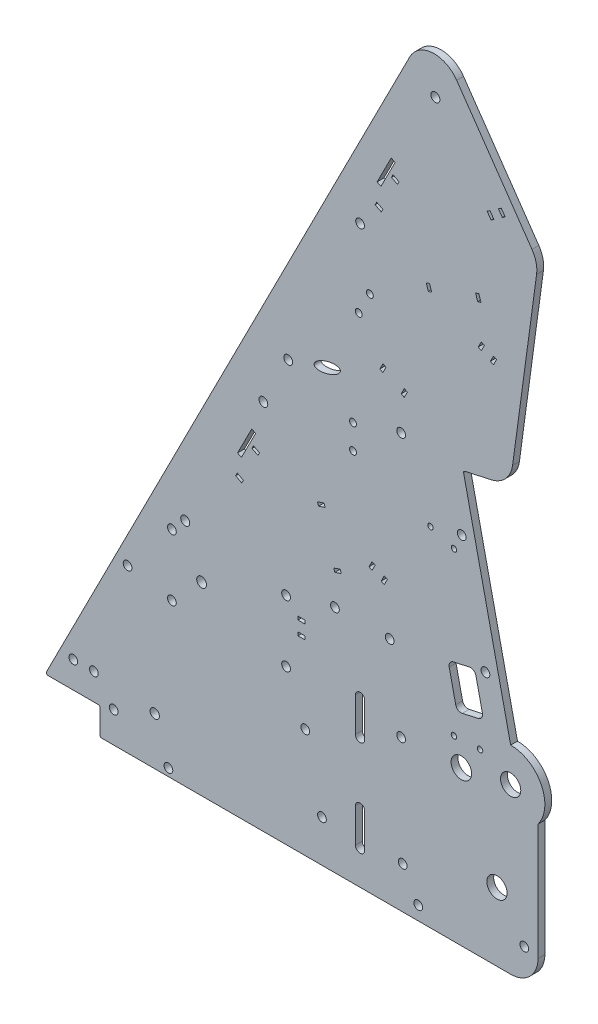
SolidWorks part; units mm, degrees
other "Markup1"
sketch "Sketch5"
ref_plane "Front Plane" through (0, 0, 0) normal (0, 0, 1) x (1, 0, 0)
ref_plane "Top Plane" through (0, 0, 0) normal (0, 1, 0) x (1, 0, 0)
ref_plane "Right Plane" through (0, 0, 0) normal (1, 0, 0) x (0, 0, -1)
sketch "Sketch1" plane through (0, 0, 0) normal (0, 0, 1) x (1, 0, 0)
  line L1 (228.6, -12.7) -> (228.6, 53.975)
  line L2 (178.7547, 351.4131) -> (0, 0)
  line L3 (228.6, 279.4) -> (178.7547, 351.4131)
  line L5 (0, 0) -> (25.4, 0)
  line L6 (25.4, 0) -> (25.4, -12.7)
  line L7 (25.4, -12.7) -> (228.6, -12.7)
  line L9 (215.9, 79.375) -> (193.9097, 178.5667)
  line L10 (193.9097, 178.5667) -> (215.6079, 183.377)
  line L11 (215.6079, 183.377) -> (228.6, 279.4)
  arc A0 (228.6, 53.975) -> (215.9, 79.375) centre (215.9, 63.5) ccw
  dimension "D7" = 12.7
  dimension "D8" = 76.2
  dimension "D10" = 31.75
  dimension "D2" = 292.1
  dimension "D3" = 25.4
  dimension "D4" = 215.9
  dimension "D5" = 394.2644
  dimension "D6" = 203.2
  dimension "D9" = 63.039
  dimension "D11" = 101.6
  dimension "D12" = 12.5
  dimension "D13" = 22.225
extrude "Boss-Extrude1" add sketch "Sketch1" along normal blind 3.175
sketch "Sketch2" plane through (0, 0, 3.175) normal (0, 0, 1) x (1, 0, 0)
  line L0 (178.7547, 351.4131) -> (0, 0) construction
  line L1 (25.4, -12.7) -> (228.6, -12.7) construction
  line L2 (215.9, 79.375) -> (193.9097, 178.5667) construction
  line L3 (193.9097, 178.5667) -> (215.6079, 183.377) construction
  line L4 (215.9, 79.375) -> (193.9097, 178.5667) construction
  line L5 (64.9432, 94.0578) -> (72.5445, 73.1732) construction
  line L6 (64.9432, 94.0578) -> (103.3734, 94.0578) construction
  line L10 (228.6, -12.7) -> (228.6, 53.975) construction
  circle A0 centre (64.9432, 94.0578) radius 2.0955
  circle A1 centre (180.975, 322.1643) radius 2.0955
  circle A2 centre (72.5445, 73.1732) radius 2.286
  circle A3 centre (193.2078, 152.3944) radius 2.032
  circle A4 centre (215.9, 63.5) radius 4.699
  circle A7 centre (173.0375, -6.35) radius 2.032
  circle A8 centre (204.203, 102.7985) radius 2.032
  circle A26 centre (209.55, 19.05) radius 4.699
  arc A30 (228.6, 53.975) -> (215.9, 79.375) centre (215.9, 63.5) ccw construction
  circle A31 centre (165.1, 179.3875) radius 2.032
  circle A35 centre (111.724, 87.4607) radius 2.032
  circle A36 centre (111.724, 58.8857) radius 2.032
  circle A37 centre (58.765, 58.8857) radius 2.032
  circle A38 centre (58.765, 87.4607) radius 2.032
  circle A39 centre (111.724, 58.8857) radius 1.905 construction
  circle A42 centre (111.724, 87.4607) radius 1.905 construction
  circle A43 centre (58.765, 58.8857) radius 1.905 construction
  circle A44 centre (58.765, 87.4607) radius 1.905 construction
  dimension "D3" = 4.191
  dimension "D5" = 4.191
  dimension "D9" = 4.572
  dimension "D20" = 9.398
  dimension "D23" = 9.398
  dimension "D18" = 4.064
  dimension "D26" = 4.064
  dimension "D14" = 4.064
  dimension "D10" = 4.064
  dimension "D2" = 15.24
  dimension "D6" = 15.24
  dimension "D7" = 22.225
  dimension "D21" = 44.45
  dimension "D22" = 6.35
  dimension "D19" = 160.3375
  dimension "D24" = 44.45
  dimension "D25" = 6.35
  dimension "D27" = 25.4
  dimension "D28" = 50.8
  dimension "D29" = 6.35
  dimension "D17" = 6.35
  dimension "D33" = 55.5625
  dimension "D15" = 114.3
  dimension "D4" = 180.975
  dimension "D8" = 70
extrude "Cut-Extrude1" cut sketch "Sketch2" against normal through all
sketch "Sketch7" plane through (0, 0, 3.175) normal (0, 0, 1) x (1, 0, 0)
  line L0 (146.05, 3.175) -> (146.05, 19.05) construction
  line L1 (143.891, 3.175) -> (143.891, 19.05)
  line L2 (148.209, 3.175) -> (148.209, 19.05)
  line L3 (146.05, 47.625) -> (146.05, 63.5) construction
  line L4 (143.891, 47.625) -> (143.891, 63.5)
  line L5 (148.209, 47.625) -> (148.209, 63.5)
  line L6 (25.4, -12.7) -> (228.6, -12.7) construction
  line L12 (228.6, -12.7) -> (228.6, 53.975) construction
  line L13 (25.4, -12.7) -> (228.6, -12.7) construction
  arc A0 (143.891, 3.175) -> (148.209, 3.175) centre (146.05, 3.175) ccw
  arc A1 (148.209, 19.05) -> (143.891, 19.05) centre (146.05, 19.05) ccw
  arc A2 (143.891, 47.625) -> (148.209, 47.625) centre (146.05, 47.625) ccw
  arc A3 (148.209, 63.5) -> (143.891, 63.5) centre (146.05, 63.5) ccw
  circle A8 centre (50.8, 9.525) radius 2.159
  point P2 (146.05, 11.1125)
  point P9 (146.05, 55.5625)
  dimension "D1" = 4.318
  dimension "D5" = 4.318
  dimension "D2" = 15.875
  dimension "D3" = 15.875
  dimension "D4" = 44.45
  dimension "D6" = 95.25
  dimension "D7" = 82.55
  dimension "D8" = 15.875
  dimension "D9" = 22.225
extrude "Cut-Extrude2" cut sketch "Sketch7" against normal through all
sketch "Sketch10" plane through (0, 0, 3.175) normal (0, 0, 1) x (1, 0, 0)
  circle A0 centre (120.65, 38.1) radius 2.032
  circle A1 centre (165.1, 57.15) radius 2.032
  circle A2 centre (13.0465, 12.3347) radius 2.032
  circle A3 centre (22.5715, 12.3347) radius 2.032
  circle A4 centre (38.2114, 62.6398) radius 2.032
  dimension "D1" = 4.064
  dimension "D3" = 38.1
  dimension "D2" = 120.65
  dimension "D4" = 63.5
  dimension "D5" = 69.85
extrude "Cut-Extrude3" cut sketch "Sketch10" against normal up to next
fillet "Fillet1" radius 12.7 4 edges at (228.6, -12.7, 1.5875) (178.7547, 351.4131, 1.5875) (215.6079, 183.377, 1.5875) (228.6, 279.4, 1.5875)
fillet "Fillet2" radius 0.7937 4 edges at (25.4, -12.7, 1.5875) (25.4, 0, 1.5875) (193.9097, 178.5667, 1.5875) (0, 0, 1.5875)
sketch "Sketch12" plane through (0, 0, 3.175) normal (0, 0, 1) x (1, 0, 0)
  circle A0 centre (31.75, 1.5875) radius 2.032
  circle A1 centre (173.0375, -6.35) radius 2.032
  circle A2 centre (222.25, 1.5875) radius 2.032
  circle A3 centre (57.15, -9.2075) radius 2.032
  circle A4 centre (57.15, -9.2075) radius 2.286 construction
  dimension "D1" = 4.064
  dimension "D2" = 4.064
extrude "Cut-Extrude5" cut sketch "Sketch12" against normal through all
sketch "Sketch13" plane through (0, 0, 3.175) normal (0, 0, 1) x (1, 0, 0)
  line L0 (94.4669, 139.2838) -> (96.8293, 143.928) construction
  line L1 (228.6, 0) -> (228.6, 53.975) construction
  line L2 (1.2943, 0) -> (24.6062, 0) construction
  line L3 (26.1937, -12.7) -> (215.9, -12.7) construction
  line L4 (92.6843, 140.1906) -> (95.0467, 144.8348) construction
  line L8 (178.2697, 245.9923) -> (176.7582, 245.5069)
  line L9 (179.2404, 242.9693) -> (178.2697, 245.9923)
  line L10 (177.7289, 242.4839) -> (179.2404, 242.9693)
  line L11 (176.7582, 245.5069) -> (177.7289, 242.4839)
  line L12 (178.2697, 245.9923) -> (176.7582, 245.5069)
  line L13 (179.2404, 242.9693) -> (178.2697, 245.9923)
  line L14 (177.7289, 242.4839) -> (179.2404, 242.9693)
  line L15 (176.7582, 245.5069) -> (177.7289, 242.4839)
  line L16 (153.9381, 274.6148) -> (160.5022, 287.5193)
  line L17 (200.6096, 249.8308) -> (202.1211, 250.3161)
  line L18 (199.639, 252.8538) -> (200.6096, 249.8308)
  line L19 (201.1505, 253.3391) -> (199.639, 252.8538)
  line L20 (202.1211, 250.3161) -> (201.1505, 253.3391)
  line L21 (200.6096, 249.8308) -> (202.1211, 250.3161)
  line L22 (199.639, 252.8538) -> (200.6096, 249.8308)
  line L23 (201.1505, 253.3391) -> (199.639, 252.8538)
  line L24 (202.1211, 250.3161) -> (201.1505, 253.3391)
  line L25 (153.9381, 274.6148) -> (155.7207, 273.708)
  line L26 (160.5905, 279.7801) -> (163.4204, 278.3406)
  line L27 (161.3102, 281.1951) -> (160.5905, 279.7801)
  line L28 (164.1402, 279.7556) -> (161.3102, 281.1951)
  line L29 (163.4204, 278.3406) -> (164.1402, 279.7556)
  line L30 (160.5905, 279.7801) -> (163.4204, 278.3406)
  line L31 (161.3102, 281.1951) -> (160.5905, 279.7801)
  line L32 (164.1402, 279.7556) -> (161.3102, 281.1951)
  line L33 (163.4204, 278.3406) -> (164.1402, 279.7556)
  line L34 (160.5022, 287.5193) -> (162.2849, 286.6125)
  line L35 (155.7207, 273.708) -> (162.2849, 286.6125)
  line L36 (153.7897, 266.4104) -> (153.0699, 264.9954)
  line L37 (156.6196, 264.9709) -> (153.7897, 266.4104)
  line L38 (155.8998, 263.5559) -> (156.6196, 264.9709)
  line L39 (153.0699, 264.9954) -> (155.8998, 263.5559)
  line L40 (153.7897, 266.4104) -> (153.0699, 264.9954)
  line L41 (156.6196, 264.9709) -> (153.7897, 266.4104)
  line L42 (155.8998, 263.5559) -> (156.6196, 264.9709)
  line L43 (153.0699, 264.9954) -> (155.8998, 263.5559)
  line L44 (157.3929, 281.4066) -> (159.7553, 286.0508) construction
  line L45 (159.1755, 280.4999) -> (161.5379, 285.1441) construction
  line L46 (169.4256, 275.2859) -> (159.1755, 280.4999) construction
  line L47 (89.2295, 133.3988) -> (95.7936, 146.3032)
  line L48 (89.2295, 133.3988) -> (91.0121, 132.492)
  line L49 (95.7936, 146.3032) -> (97.5763, 145.3965)
  line L50 (91.0121, 132.492) -> (97.5763, 145.3965)
  line L51 (96.6016, 139.979) -> (99.4315, 138.5395)
  line L52 (96.6016, 139.979) -> (95.8819, 138.5641)
  line L53 (99.4315, 138.5395) -> (98.7118, 137.1246)
  line L54 (95.8819, 138.5641) -> (98.7118, 137.1246)
  line L55 (89.0811, 125.1944) -> (91.911, 123.7549)
  line L56 (89.0811, 125.1944) -> (88.3613, 123.7794)
  line L57 (91.911, 123.7549) -> (91.1912, 122.3399)
  line L58 (88.3613, 123.7794) -> (91.1912, 122.3399)
  line L59 (126.3022, 132.31) -> (126.8, 130.8026)
  line L60 (126.3022, 132.31) -> (129.3171, 133.3057)
  line L61 (126.8, 130.8026) -> (129.8149, 131.7982)
  line L62 (129.3171, 133.3057) -> (129.8149, 131.7982)
  line L63 (133.8383, 109.4909) -> (134.3361, 107.9835)
  line L64 (133.8383, 109.4909) -> (136.8531, 110.4866)
  line L65 (134.3361, 107.9835) -> (137.351, 108.9791)
  line L66 (136.8531, 110.4866) -> (137.351, 108.9791)
  line L67 (94.4669, 139.2838) -> (104.717, 134.0699) construction
  line L68 (87.6661, 125.9141) -> (97.9162, 120.7002) construction
  line L69 (123.7602, 119.8953) -> (130.9237, 133.9781) construction
  line L70 (123.5341, 132.4639) -> (128.7928, 129.7889) construction
  line L71 (139.302, 109.2409) -> (134.8604, 111.5002) construction
  line L72 (133.3189, 108.4697) -> (134.8604, 111.5002) construction
  line L122 (203.7094, 233.8371) -> (202.2945, 234.5568)
  line L123 (202.2699, 231.0072) -> (203.7094, 233.8371)
  line L124 (200.855, 231.7269) -> (202.2699, 231.0072)
  line L125 (202.2945, 234.5568) -> (200.855, 231.7269)
  line L126 (203.7094, 233.8371) -> (202.2945, 234.5568)
  line L127 (202.2699, 231.0072) -> (203.7094, 233.8371)
  line L128 (200.855, 231.7269) -> (202.2699, 231.0072)
  line L129 (202.2945, 234.5568) -> (200.855, 231.7269)
  line L130 (206.5148, 228.8479) -> (207.9298, 228.1282)
  line L131 (207.9543, 231.6778) -> (206.5148, 228.8479)
  line L132 (209.3693, 230.9581) -> (207.9543, 231.6778)
  line L133 (207.9298, 228.1282) -> (209.3693, 230.9581)
  line L134 (206.5148, 228.8479) -> (207.9298, 228.1282)
  line L135 (207.9543, 231.6778) -> (206.5148, 228.8479)
  line L136 (209.3693, 230.9581) -> (207.9543, 231.6778)
  line L137 (207.9298, 228.1282) -> (209.3693, 230.9581)
  line L138 (211.5405, 292.889) -> (210.2352, 291.9855)
  line L139 (213.3475, 290.2784) -> (211.5405, 292.889)
  line L140 (212.0422, 289.3749) -> (213.3475, 290.2784)
  line L141 (210.2352, 291.9855) -> (212.0422, 289.3749)
  line L142 (211.5405, 292.889) -> (210.2352, 291.9855)
  line L143 (213.3475, 290.2784) -> (211.5405, 292.889)
  line L144 (212.0422, 289.3749) -> (213.3475, 290.2784)
  line L145 (210.2352, 291.9855) -> (212.0422, 289.3749)
  line L146 (206.3193, 289.275) -> (205.014, 288.3715)
  line L147 (208.1263, 286.6644) -> (206.3193, 289.275)
  line L148 (206.821, 285.7609) -> (208.1263, 286.6644)
  line L149 (205.014, 288.3715) -> (206.821, 285.7609)
  line L150 (206.3193, 289.275) -> (205.014, 288.3715)
  line L151 (208.1263, 286.6644) -> (206.3193, 289.275)
  line L152 (206.821, 285.7609) -> (208.1263, 286.6644)
  line L153 (205.014, 288.3715) -> (206.821, 285.7609)
  line L187 (155.2281, 200.1197) -> (156.643, 199.3999)
  line L188 (156.6676, 202.9496) -> (155.2281, 200.1197)
  line L189 (158.0826, 202.2298) -> (156.6676, 202.9496)
  line L190 (156.643, 199.3999) -> (158.0826, 202.2298)
  line L191 (155.2281, 200.1197) -> (156.643, 199.3999)
  line L192 (156.6676, 202.9496) -> (155.2281, 200.1197)
  line L193 (158.0826, 202.2298) -> (156.6676, 202.9496)
  line L194 (156.643, 199.3999) -> (158.0826, 202.2298)
  line L196 (165.1328, 195.0814) -> (166.5478, 194.3617)
  line L197 (166.5723, 197.9113) -> (165.1328, 195.0814)
  line L198 (167.9873, 197.1916) -> (166.5723, 197.9113)
  line L199 (166.5478, 194.3617) -> (167.9873, 197.1916)
  line L200 (165.1328, 195.0814) -> (166.5478, 194.3617)
  line L201 (166.5723, 197.9113) -> (165.1328, 195.0814)
  line L202 (167.9873, 197.1916) -> (166.5723, 197.9113)
  line L203 (166.5478, 194.3617) -> (167.9873, 197.1916)
  line L280 (151.6296, 120.9493) -> (150.1901, 118.1193)
  line L281 (151.6296, 120.9493) -> (153.0445, 120.2295)
  line L282 (150.1901, 118.1193) -> (151.605, 117.3996)
  line L283 (153.0445, 120.2295) -> (151.605, 117.3996)
  line L284 (155.8499, 115.2403) -> (157.2894, 118.0702)
  line L285 (155.8499, 115.2403) -> (157.2649, 114.5206)
  line L286 (157.2894, 118.0702) -> (158.7044, 117.3505)
  line L287 (157.2649, 114.5206) -> (158.7044, 117.3505)
  line L288 (117.2485, 81.8727) -> (120.4235, 81.8727)
  line L289 (117.2485, 81.8727) -> (117.2485, 80.2852)
  line L290 (120.4235, 81.8727) -> (120.4235, 80.2852)
  line L291 (117.2485, 80.2852) -> (120.4235, 80.2852)
  line L292 (117.2485, 75.5227) -> (120.4235, 75.5227)
  line L293 (117.2485, 75.5227) -> (117.2485, 73.9352)
  line L294 (120.4235, 75.5227) -> (120.4235, 73.9352)
  line L295 (117.2485, 73.9352) -> (120.4235, 73.9352)
  line L296 (140.3458, 109.2709) -> (148.2756, 124.8601) construction
  line L297 (115.661, 86.2542) -> (115.661, 60.0922) construction
  line L298 (59.9715, 91.3977) -> (110.5175, 91.3977) construction
  circle A0 centre (112.7125, 182.5625) radius 2.032
  circle A1 centre (146.05, 254) radius 2.032
  circle A2 centre (101.1964, 159.9231) radius 2.032 construction
  circle A3 centre (101.1964, 159.9231) radius 2.032
  circle A4 centre (145.4254, 217.7376) radius 1.6 construction
  circle A5 centre (150.594, 227.8985) radius 1.6 construction
  circle A7 centre (145.4254, 217.7376) radius 1.6
  circle A8 centre (150.594, 227.8985) radius 1.6
  circle A9 centre (142.7746, 160.9907) radius 1.6 construction
  circle A10 centre (142.7746, 172.3907) radius 1.6 construction
  circle A11 centre (142.7746, 160.9907) radius 1.6
  circle A12 centre (142.7746, 172.3907) radius 1.6
  ellipse E0 centre (130.8261, 188.4615) end of major axis (136.864, 190.4279) minor radius 2.3812 construction
  ellipse E1 centre (130.8261, 188.4615) end of major axis (136.864, 190.4279) minor radius 2.3812
  point P89 (96.2418, 139.2716)
  dimension "D2" = 4.064
  dimension "D5" = 4.064
  dimension "D1" = 195.2625
  dimension "D3" = 82.55
  dimension "D4" = 254
  dimension "D6" = 115.8875
  dimension "D11" = 6.858
  dimension "D12" = 7.62
  dimension "D13" = 1.5875
  dimension "D14" = 3.175
  dimension "D15" = 1.5875
  dimension "D16" = 6.858
  dimension "D17" = 7.62
  dimension "D24" = 1.5875
  dimension "D25" = 3.175
  dimension "D26" = 4.7625
  dimension "D27" = 4.7625
  dimension "D28" = 9.525
  dimension "D29" = 3.175
  dimension "D30" = 1.5875
  dimension "D31" = 4.7625
  dimension "D32" = 1.5875
  dimension "D33" = 9.525
  dimension "D7" = 0
  dimension "D8" = 0
  dimension "D9" = 0
  dimension "D10" = 0
  dimension "D18" = 0
  dimension "D19" = 0
  dimension "D20" = 0
  dimension "D21" = 0
  dimension "D22" = 0
  dimension "D23" = 0
extrude "Cut-Extrude6" cut sketch "Sketch13" against normal through all
sketch "Sketch14" plane through (0, 0, 3.175) normal (0, 0, 1) x (1, 0, 0)
  line L5 (186.8444, 98.9502) -> (199.2434, 101.699)
  line L6 (186.8444, 98.9502) -> (190.9676, 80.3518)
  line L7 (190.9676, 80.3518) -> (203.3665, 83.1006)
  line L8 (199.2434, 101.699) -> (203.3665, 83.1006)
  line L14 (202.8168, 85.5804) -> (199.7931, 99.2192) construction
  line L15 (193.4474, 80.9015) -> (200.8868, 82.5508) construction
  line L16 (187.3942, 96.4704) -> (190.4178, 82.8316) construction
  line L17 (196.7636, 101.1493) -> (189.3242, 99.5) construction
  circle A0 centre (189.6022, 69.9806) radius 1.27
  circle A1 centre (201.7089, 70.5092) radius 1.27
  circle A2 centre (189.6022, 69.9806) radius 1.27 construction
  circle A3 centre (201.7089, 70.5092) radius 1.27 construction
  circle A4 centre (159.7935, 93.98) radius 2.032
  circle A5 centre (134.3935, 93.98) radius 2.032
  circle A6 centre (178.7216, 148.5324) radius 1.27
  circle A8 centre (178.7216, 148.5324) radius 1.27 construction
  circle A9 centre (189.6226, 145.0954) radius 1.27
  circle A10 centre (189.6226, 145.0954) radius 1.27 construction
  circle A11 centre (128.361, 6.6675) radius 2.032
  circle A12 centre (165.826, 6.6675) radius 2.032
  point P8 (152.4, 88.9)
  dimension "D1" = 4.064
extrude "Cut-Extrude7" cut sketch "Sketch14" against normal through all both and the other way through all
fillet "Fillet3" radius 2.54 4 edges at (199.2434, 101.699, 1.5875) (186.8444, 98.9502, 1.5875) (190.9676, 80.3518, 1.5875) (203.3665, 83.1006, 1.5875)
sketch "Sketch15" plane through (0, 0, 3.175) normal (0, 0, 1) x (1, 0, 0)
  circle A0 centre (193.04, 58.801) radius 4.7625 construction
  circle A1 centre (193.04, 58.801) radius 4.7625
extrude "Cut-Extrude8" cut sketch "Sketch15" against normal through all
equation "\"D6@Sketch2\"=\"D2@Sketch2\""
